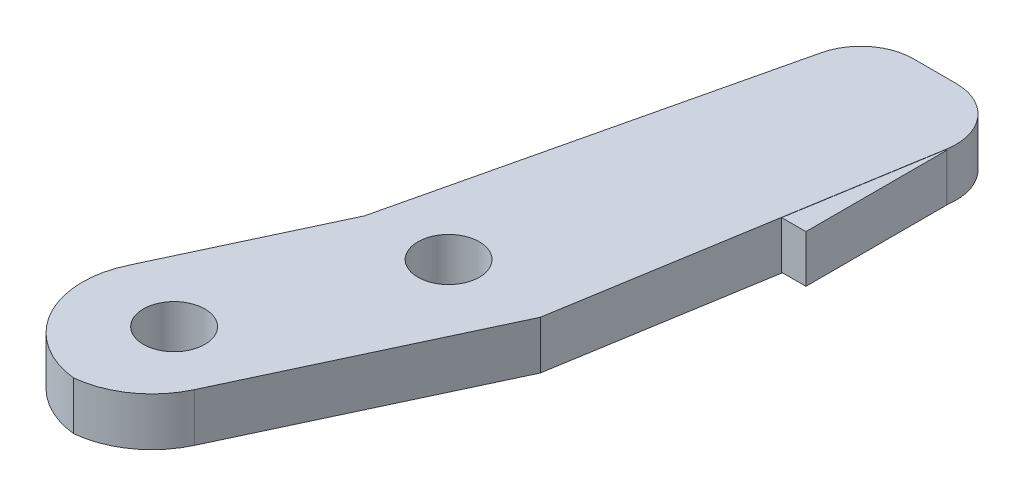
SolidWorks part; units mm, degrees
ref_plane "Front Plane" through (0, 0, 0) normal (0, 0, 1) x (1, 0, 0)
ref_plane "Top Plane" through (0, 0, 0) normal (0, 1, 0) x (1, 0, 0)
ref_plane "Right Plane" through (0, 0, 0) normal (1, 0, 0) x (0, 0, -1)
sketch "Sketch1" plane through (0, 0, 0) normal (0, 1, 0) x (1, 0, 0)
  line L0 (0, 0) -> (7.6273, 16.3041)
  line L1 (7.6273, 16.3041) -> (13.1317, 39.6644)
  line L6 (17.6273, 16.3041) -> (10, 0)
  line L7 (10, 0) -> (0, 0)
  line L9 (17.6273, 16.3041) -> (21.4772, 39.6644)
  line L10 (21.4772, 39.6644) -> (13.1317, 39.6644)
  dimension "D1" = 10
  dimension "D2" = 18
  dimension "D3" = 18
  dimension "D4" = 24
extrude "Boss-Extrude1" add sketch "Sketch1" along normal blind 2.75
fillet "Fillet1" radius 5 2 edges at (10, 1.375, 0) (0, 1.375, 0)
fillet "Fillet2" radius 3 2 edges at (13.1317, 1.375, -39.6644) (21.4772, 1.375, -39.6644)
sketch "Sketch2" plane through (0, 2.75, 0) normal (0, 1, 0) x (1, 0, 0)
  circle A0 centre (7.6677, 5.4139) radius 1.75
  circle A1 centre (12.17, 16.5373) radius 1.75
  dimension "D1" = 3.5
  dimension "D2" = 3.5
  dimension "D3" = 12
extrude "Cut-Extrude1" cut sketch "Sketch2" against normal through all
ref_plane "Plane1" through (20.95, 0, 0) normal (1, 0, 0) x (0, 0, -1)
sketch "Sketch4" plane through (20.95, -0.8558, -2.8607) normal (1, 0, 0) x (0, 0, -1)
  line L1 (33.2372, 3.5919) -> (25.2372, 3.5919)
  line L2 (33.2372, 3.5919) -> (33.2372, 0.8919)
  line L3 (33.2372, 0.8919) -> (25.2372, 0.8919)
  line L4 (25.2372, 3.5919) -> (25.2372, 0.8919)
  dimension "D1" = 2.7
  dimension "D2" = 8
extrude "Boss-Extrude2" add sketch "Sketch4" against normal up to surface (0.0606 mm away) up to face at (19.2648, 1.375, -26.2403)
extrude "Boss-Extrude3" add sketch "Sketch4<2>" against normal up to surface (0.0606 mm away) up to face at (20.2302, 1.3861, -32.0979)
sketch "Sketch4<2>" plane through (20.95, -0.8558, -2.8607) normal (1, 0, 0) x (0, 0, -1) same geometry as "Sketch4"
